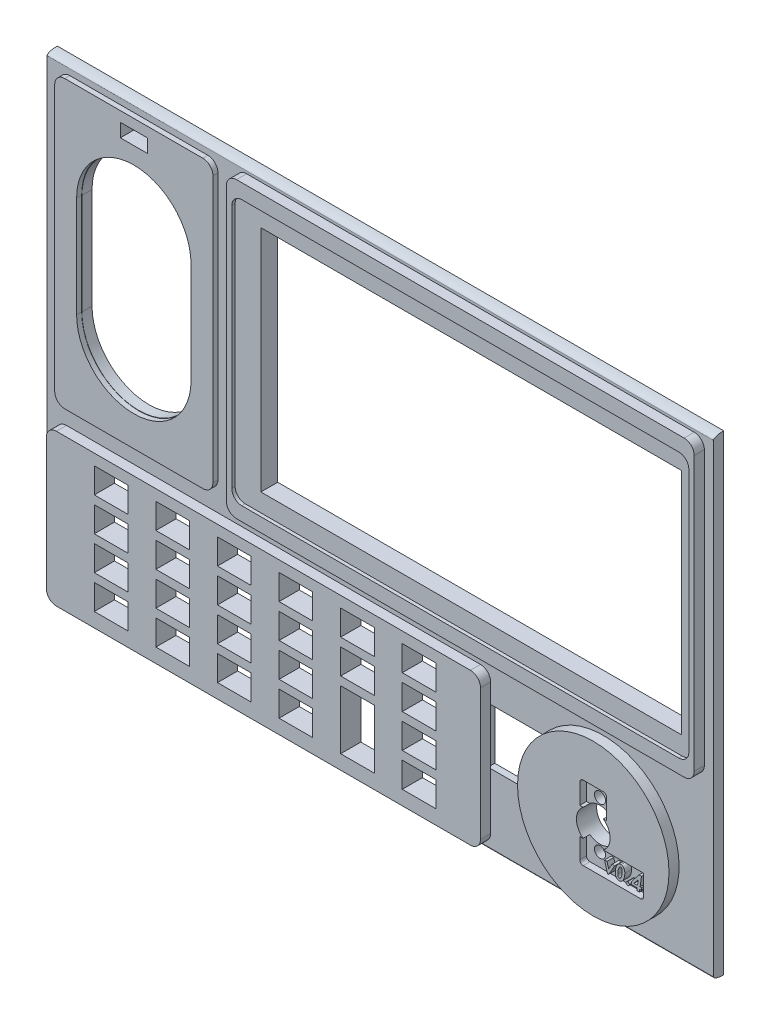
SolidWorks part; units mm, degrees
ref_plane "Front Plane" through (0, 0, 0) normal (0, 0, 1) x (1, 0, 0)
ref_plane "Top Plane" through (0, 0, 0) normal (0, 1, 0) x (1, 0, 0)
ref_plane "Right Plane" through (0, 0, 0) normal (1, 0, 0) x (0, 0, -1)
sketch "Sketch1" plane through (0, 0, 0) normal (0, 0, 1) x (1, 0, 0)
  line L1 (99, -70) -> (-99, -70)
  line L2 (99, -70) -> (99, 70)
  line L3 (99, 70) -> (-99, 70)
  line L4 (-99, -70) -> (-99, 70)
  line L5 (99, -70) -> (-99, 70) construction
  line L6 (99, 70) -> (-99, -70) construction
  point P0 (0, 0)
  dimension "D1" = 198
  dimension "D2" = 140
extrude "main_body" add sketch "Sketch1" along normal blind 3
fillet "long_corners" radius 3 2 edges at (0, 70, 3) (0, -70, 3) second distance 1 first distance on face at (0, 70, 1.5) first distance on face at (0, -70, 1.5)
sketch "Sketch2" plane through (0, 0, 3) normal (0, 0, 1) x (1, 0, 0)
  line L0 (-99, 24.75) -> (99, 24.75) construction
  line L1 (-99, 69) -> (-99, -69) construction
  line L2 (99, -69) -> (99, 69) construction
  line L3 (99, 69) -> (-99, 69) construction
  line L4 (-48.25, -17.75) -> (-95.25, -17.75)
  line L5 (-48.25, -17.75) -> (-48.25, 67.25)
  line L6 (-48.25, 67.25) -> (-95.25, 67.25)
  line L7 (-95.25, -17.75) -> (-95.25, 67.25)
  line L8 (-48.25, -17.75) -> (-95.25, 67.25) construction
  line L9 (-48.25, 67.25) -> (-95.25, -17.75) construction
  point P6 (-71.75, 24.75)
  dimension "D1" = 85
  dimension "D2" = 47
  dimension "D3" = 27.25
  dimension "D4" = 44.25
extrude "speaker" add sketch "Sketch2" along normal blind 1.5
fillet "speaker_corners" radius 3 4 edges at (-95.25, 67.25, 3.75) (-95.25, -17.75, 3.75) (-48.25, -17.75, 3.75) (-48.25, 67.25, 3.75)
sketch "Sketch19" plane through (0, 0, 4.5) normal (0, 0, 1) x (1, 0, 0)
  line L0 (-71.75, 67.25) -> (-71.75, -17.75) construction
  line L1 (-51.25, 67.25) -> (-92.25, 67.25) construction
  line L2 (-92.25, -17.75) -> (-51.25, -17.75) construction
  line L3 (-71.75, 8.25) -> (-71.75, 38.25) construction
  line L4 (-95.25, 64.25) -> (-95.25, -14.75) construction
  line L5 (-95.25, 24.75) -> (-48.25, 24.75) construction
  line L6 (-48.25, -14.75) -> (-48.25, 64.25) construction
  line L7 (-88.75, 8.25) -> (-88.75, 38.25)
  line L8 (-54.75, 8.25) -> (-54.75, 38.25)
  arc A0 (-88.75, 8.25) -> (-54.75, 8.25) centre (-71.75, 8.25) ccw
  arc A1 (-54.75, 38.25) -> (-88.75, 38.25) centre (-71.75, 38.25) ccw
  point P14 (-71.75, 23.25)
  point P19 (-71.75, -8.75)
  point P20 (-71.75, 55.25)
  dimension "D2" = 64
  dimension "D1" = 34
  dimension "D3" = 12
extrude "speaker_cut" cut sketch "Sketch19" against normal through all
sketch "Sketch21" plane through (0, 0, 0) normal (0, 0, -1) x (-1, 0, 0)
  line L0 (71.75, -8.75) -> (71.75, 55.25) construction
  line L2 (54.75, 8.25) -> (54.75, 38.25) construction
  line L3 (54.75, 23.25) -> (88.75, 23.25) construction
  line L4 (88.75, 38.25) -> (88.75, 8.25) construction
  line L5 (50.25, 59.25) -> (93.25, 59.25)
  line L6 (50.25, 59.25) -> (50.25, -12.75)
  line L7 (50.25, -12.75) -> (93.25, -12.75)
  line L8 (93.25, 59.25) -> (93.25, -12.75)
  line L9 (50.25, 59.25) -> (93.25, -12.75) construction
  line L10 (50.25, -12.75) -> (93.25, 59.25) construction
  arc A0 (54.75, 8.25) -> (88.75, 8.25) centre (71.75, 8.25) ccw construction
  arc A1 (88.75, 38.25) -> (54.75, 38.25) centre (71.75, 38.25) ccw construction
  point P14 (71.75, 23.25)
  dimension "D1" = 43
  dimension "D2" = 72
extrude "speaker_slot" cut sketch "Sketch21" against normal blind 3
sketch "Sketch36" plane through (0, 0, 3) normal (0, 0, -1) x (-1, 0, 0)
  line L0 (50.25, 23.25) -> (93.25, 23.25) construction
  line L1 (50.25, 59.25) -> (50.25, -12.75) construction
  line L2 (71.75, 8.2639) -> (71.75, 38.2361) construction
  line L3 (71.75, 8.2639) -> (71.75, 38.2361) construction
  line L4 (93.25, -12.75) -> (93.25, 59.25) construction
  line L5 (50.25, 59.25) -> (50.25, -12.75) construction
  line L6 (54.8316, 8.2639) -> (54.8316, 38.2361)
  line L9 (88.6684, 8.2639) -> (88.6684, 38.2361)
  line L10 (54.25, 8.2639) -> (54.25, 38.2361)
  line L11 (89.25, 8.2639) -> (89.25, 38.2361)
  line L12 (93.25, 59.25) -> (50.25, 59.25) construction
  line L13 (71.75, 59.25) -> (71.75, -12.75) construction
  line L14 (50.25, -12.75) -> (93.25, -12.75) construction
  line L23 (50.25, 57.25) -> (93.25, 57.25)
  line L25 (50.25, 57.25) -> (50.25, 56.75)
  line L26 (93.25, -0.25) -> (87.75, -0.25)
  line L27 (50.25, 56.75) -> (93.25, 56.75)
  line L28 (93.25, 57.25) -> (93.25, 56.75)
  line L37 (93.25, -12.75) -> (93.25, 59.25) construction
  line L38 (93.25, -0.25) -> (93.25, 0.25)
  line L39 (93.25, 0.25) -> (87.75, 0.25)
  line L48 (93.25, -10.75) -> (50.25, -10.75)
  line L49 (93.25, -10.75) -> (93.25, -10.25)
  line L50 (93.25, -10.25) -> (50.25, -10.25)
  line L51 (50.25, -10.75) -> (50.25, -10.25)
  line L52 (93.25, 46.75) -> (87.75, 46.75)
  line L53 (93.25, 46.75) -> (93.25, 46.25)
  line L54 (93.25, 46.25) -> (87.75, 46.25)
  line L55 (87.75, 46.75) -> (87.75, 46.25)
  line L56 (93.25, 35.25) -> (89.75, 35.25)
  line L57 (93.25, 35.25) -> (93.25, 34.75)
  line L58 (93.25, 34.75) -> (89.75, 34.75)
  line L59 (89.75, 35.25) -> (89.75, 34.75)
  line L60 (93.25, 23.25) -> (89.75, 23.25)
  line L61 (93.25, 23.25) -> (93.25, 23.75)
  line L62 (93.25, 23.75) -> (89.75, 23.75)
  line L63 (89.75, 23.25) -> (89.75, 23.75)
  line L64 (93.25, 10.75) -> (89.75, 10.75)
  line L65 (93.25, 10.75) -> (93.25, 11.25)
  line L66 (93.25, 11.25) -> (89.75, 11.25)
  line L67 (89.75, 10.75) -> (89.75, 11.25)
  line L68 (87.75, -0.25) -> (87.75, 0.25)
  line L69 (93.25, -5.25) -> (83.25, -5.25)
  line L70 (93.25, -5.25) -> (93.25, -5.75)
  line L71 (93.25, -5.75) -> (83.25, -5.75)
  line L72 (83.25, -5.25) -> (83.25, -5.75)
  line L73 (93.25, 52.25) -> (83.25, 52.25)
  line L74 (93.25, 52.25) -> (93.25, 51.75)
  line L75 (93.25, 51.75) -> (83.25, 51.75)
  line L76 (83.25, 52.25) -> (83.25, 51.75)
  line L77 (50.25, 52.25) -> (60.25, 52.25)
  line L78 (50.25, 52.25) -> (50.25, 51.75)
  line L79 (50.25, 51.75) -> (60.25, 51.75)
  line L80 (60.25, 52.25) -> (60.25, 51.75)
  line L81 (50.25, 46.75) -> (55.75, 46.75)
  line L82 (50.25, 46.75) -> (50.25, 46.25)
  line L83 (50.25, 46.25) -> (55.75, 46.25)
  line L84 (55.75, 46.75) -> (55.75, 46.25)
  line L85 (50.25, 35.25) -> (53.75, 35.25)
  line L86 (50.25, 35.25) -> (50.25, 34.75)
  line L87 (50.25, 34.75) -> (53.75, 34.75)
  line L88 (53.75, 35.25) -> (53.75, 34.75)
  line L89 (50.25, 23.25) -> (53.75, 23.25)
  line L90 (50.25, 23.25) -> (50.25, 23.75)
  line L91 (50.25, 23.75) -> (53.75, 23.75)
  line L92 (53.75, 23.25) -> (53.75, 23.75)
  line L93 (50.25, 10.25) -> (53.75, 10.25)
  line L94 (50.25, 10.25) -> (50.25, 10.75)
  line L95 (50.25, 10.75) -> (53.75, 10.75)
  line L96 (53.75, 10.25) -> (53.75, 10.75)
  line L97 (50.25, -0.25) -> (55.75, -0.25)
  line L98 (50.25, -0.25) -> (50.25, 0.25)
  line L99 (50.25, 0.25) -> (55.75, 0.25)
  line L100 (55.75, -0.25) -> (55.75, 0.25)
  line L101 (50.25, -5.25) -> (60.25, -5.25)
  line L102 (50.25, -5.25) -> (50.25, -5.75)
  line L103 (50.25, -5.75) -> (60.25, -5.75)
  line L104 (60.25, -5.25) -> (60.25, -5.75)
  arc A0 (54.25, 8.2639) -> (89.25, 8.2639) centre (71.75, 8.2639) ccw
  arc A1 (89.25, 38.2361) -> (54.25, 38.2361) centre (71.75, 38.2361) ccw
  arc A4 (54.8316, 8.2639) -> (88.6684, 8.2639) centre (71.75, 8.2639) ccw
  arc A5 (88.6684, 38.2361) -> (54.8316, 38.2361) centre (71.75, 38.2361) ccw
  point P6 (71.75, 23.25)
  point P22 (71.75, 23.25)
  point P31 (89.25, 23.25)
  point P32 (71.75, 55.1546)
  point P33 (71.75, -8.6546)
  point P95 (52, 35.25)
  point P96 (55.25, 51.75)
  point P97 (91.5, 10.75)
  dimension "D48" = 0.5816
  dimension "D1" = 33.8368
  dimension "D2" = 35
  dimension "D3" = 63.8091
  dimension "D4" = 0.5
  dimension "D5" = 0.5
  dimension "D6" = 0.5
  dimension "D7" = 0.5
  dimension "D8" = 0.5
  dimension "D9" = 11
  dimension "D10" = 11
  dimension "D11" = 5
  dimension "D12" = 4.5
  dimension "D13" = 10
  dimension "D14" = 5.5
  dimension "D15" = 3.5
  dimension "D16" = 3.5
  dimension "D17" = 0.5
  dimension "D18" = 0.5
  dimension "D19" = 0.5
  dimension "D20" = 0.5
  dimension "D21" = 11
  dimension "D22" = 11
  dimension "D23" = 5
  dimension "D24" = 10
  dimension "D25" = 5.5
  dimension "D26" = 3.5
  dimension "D27" = 3.5
  dimension "D28" = 0.5
  dimension "D29" = 0.5
  dimension "D30" = 0.5
  dimension "D31" = 0.5
  dimension "D32" = 0.5
  dimension "D33" = 0.5
  dimension "D34" = 0.5
  dimension "D35" = 12
  dimension "D36" = 10.5
  dimension "D37" = 5.5
  dimension "D38" = 5
  dimension "D39" = 4.5
  dimension "D40" = 3.5
  dimension "D41" = 10
  dimension "D42" = 4.5
  dimension "D43" = 5
  dimension "D44" = 10
  dimension "D45" = 3.5
  dimension "D46" = 5.5
  dimension "D47" = 10
extrude "speaker_print_support" add sketch "Sketch36" along normal blind 3
sketch "Sketch3" plane through (0, 0, 3) normal (0, 0, 1) x (1, 0, 0)
  line L0 (-99, 24.625) -> (99, 24.625) construction
  line L1 (-99, 69) -> (-99, -69) construction
  line L2 (99, -69) -> (99, 69) construction
  line L4 (-48.25, -14.75) -> (-48.25, 64.25) construction
  line L5 (96.25, -19) -> (-42.75, -19)
  line L6 (96.25, -19) -> (96.25, 68.25)
  line L7 (96.25, 68.25) -> (-42.75, 68.25)
  line L8 (-42.75, -19) -> (-42.75, 68.25)
  line L9 (96.25, -19) -> (-42.75, 68.25) construction
  line L10 (96.25, 68.25) -> (-42.75, -19) construction
  line L11 (99, 70) -> (-99, 70) construction
  point P8 (26.75, 24.625)
  dimension "D1" = 1.75
  dimension "D2" = 87.25
  dimension "D3" = 139
  dimension "D4" = 2.75
  dimension "D5" = 5.5
extrude "lcd" add sketch "Sketch3" along normal blind 3
fillet "lcd_corners" radius 3 4 edges at (96.25, -19, 4.5) (-42.75, -19, 4.5) (96.25, 68.25, 4.5) (-42.75, 68.25, 4.5)
sketch "Sketch9" plane through (0, 0, 6) normal (0, 0, 1) x (1, 0, 0)
  line L0 (-42.75, 24.5) -> (96.25, 24.5) construction
  line L1 (-42.75, 65.25) -> (-42.75, -16) construction
  line L2 (96.25, -16) -> (96.25, 65.25) construction
  line L3 (-39.75, -19) -> (93.25, -19) construction
  line L4 (94.65, -14.875) -> (-41.15, -14.875)
  line L5 (94.65, -14.875) -> (94.65, 63.875)
  line L6 (94.65, 63.875) -> (-41.15, 63.875)
  line L7 (-41.15, -14.875) -> (-41.15, 63.875)
  line L8 (94.65, -14.875) -> (-41.15, 63.875) construction
  line L9 (94.65, 63.875) -> (-41.15, -14.875) construction
  line L10 (93.25, 68.25) -> (-39.75, 68.25) construction
  line L11 (96.25, -16) -> (96.25, 65.25) construction
  point P6 (26.75, 24.5)
  dimension "D1" = 135.8
  dimension "D2" = 78.75
  dimension "D3" = 1.6
  dimension "D4" = 4.125
  dimension "D5" = 4.375
  dimension "D6" = 1.6
extrude "lcd_front" cut sketch "Sketch9" against normal blind 1
fillet "lcd_front_corners" radius 3 4 edges at (94.65, -14.875, 5.5) (94.65, 63.875, 5.5) (-41.15, 63.875, 5.5) (-41.15, -14.875, 5.5)
sketch "Sketch10" plane through (0, 0, 0) normal (0, 0, -1) x (-1, 0, 0)
  line L0 (-94.65, -11.875) -> (-94.65, 60.875) construction
  line L1 (-91.65, 63.875) -> (38.15, 63.875) construction
  line L2 (41.15, 63.875) -> (41.15, -14.875) construction
  line L3 (-94.65, 63.875) -> (41.15, 63.875) construction
  line L4 (33.5, -9.5) -> (-91.5, -9.5)
  line L5 (33.5, -9.5) -> (33.5, 58.5)
  line L6 (33.5, 58.5) -> (-91.5, 58.5)
  line L7 (-91.5, -9.5) -> (-91.5, 58.5)
  line L8 (-91.5, -9.5) -> (33.5, 58.5) construction
  line L9 (-91.5, 58.5) -> (33.5, -9.5) construction
  line L10 (-99, -70) -> (-99, 70) construction
  line L11 (-99, 70) -> (99, 70) construction
  line L13 (38.15, -14.875) -> (-91.65, -14.875) construction
  dimension "D1" = 125
  dimension "D2" = 68
  dimension "D3" = 7.5
  dimension "D4" = 7.65
  dimension "D5" = 11.5
  dimension "D6" = 5.375
  dimension "D7" = 3.15
  dimension "D8" = 5.375
  dimension "D9" = 5.375
extrude "lcd_back" cut sketch "Sketch10" against normal through all
sketch "Sketch4" plane through (0, 0, 3) normal (0, 0, 1) x (1, 0, 0)
  line L0 (-99, -45.75) -> (99, -45.75) construction
  line L1 (-99, 69) -> (-99, -69) construction
  line L2 (99, -69) -> (99, 69) construction
  line L4 (-92.25, -17.75) -> (-51.25, -17.75) construction
  line L5 (32.75, -68.25) -> (-96.25, -68.25)
  line L6 (32.75, -68.25) -> (32.75, -23.25)
  line L7 (32.75, -23.25) -> (-96.25, -23.25)
  line L8 (-96.25, -68.25) -> (-96.25, -23.25)
  line L9 (32.75, -68.25) -> (-96.25, -23.25) construction
  line L10 (32.75, -23.25) -> (-96.25, -68.25) construction
  line L11 (-99, -70) -> (99, -70) construction
  point P8 (-31.75, -45.75)
  dimension "D1" = 1.75
  dimension "D2" = 129
  dimension "D3" = 45
  dimension "D4" = 2.75
  dimension "D5" = 5.5
extrude "keypad" add sketch "Sketch4" along normal blind 3
fillet "keypad_corners" radius 3 4 edges at (-96.25, -68.25, 4.5) (32.75, -68.25, 4.5) (32.75, -23.25, 4.5) (-96.25, -23.25, 4.5)
sketch "Sketch25" plane through (0, 0, 6) normal (0, 0, 1) x (1, 0, 0)
  line L0 (-96.25, -30.25) -> (32.75, -30.25) construction
  line L1 (29.75, -23.25) -> (-93.25, -23.25) construction
  line L2 (-93.25, -68.25) -> (29.75, -68.25) construction
  line L3 (-77, -23.25) -> (-77, -68.25) construction
  line L5 (-35.4, -64) -> (32.75, -64) construction
  line L6 (-96.25, -26.25) -> (-96.25, -65.25) construction
  line L11 (32.75, -65.25) -> (32.75, -26.25) construction
  line L12 (-58.7, -23.25) -> (-58.7, -68.25) construction
  line L13 (-96.25, -40.25) -> (32.75, -40.25) construction
  line L14 (29.75, -23.25) -> (-93.25, -23.25) construction
  line L15 (-40.4, -23.25) -> (-40.4, -68.25) construction
  line L16 (-93.25, -68.25) -> (29.75, -68.25) construction
  line L17 (-72, -34) -> (-82, -34)
  line L18 (-22.1, -23.25) -> (-22.1, -68.25) construction
  line L19 (-96.25, -50.25) -> (32.75, -50.25) construction
  line L20 (-3.8, -23.25) -> (-3.8, -68.25) construction
  line L21 (-72, -34) -> (-72, -26.5)
  line L22 (14.5, -23.25) -> (14.5, -68.25) construction
  line L23 (-96.25, -26.25) -> (-96.25, -65.25) construction
  line L24 (-96.25, -60.25) -> (32.75, -60.25) construction
  line L25 (-72, -26.5) -> (-82, -26.5)
  line L26 (-82, -34) -> (-82, -26.5)
  line L27 (-72, -34) -> (-82, -26.5) construction
  line L28 (-72, -26.5) -> (-82, -34) construction
  line L29 (-72, -44) -> (-82, -44)
  line L30 (-72, -44) -> (-72, -36.5)
  line L31 (-72, -36.5) -> (-82, -36.5)
  line L32 (-82, -44) -> (-82, -36.5)
  line L33 (-72, -44) -> (-82, -36.5) construction
  line L34 (-72, -36.5) -> (-82, -44) construction
  line L35 (-72, -54) -> (-82, -54)
  line L36 (-72, -54) -> (-72, -46.5)
  line L37 (-72, -46.5) -> (-82, -46.5)
  line L38 (-82, -54) -> (-82, -46.5)
  line L39 (-72, -54) -> (-82, -46.5) construction
  line L40 (-72, -46.5) -> (-82, -54) construction
  line L41 (-72, -64) -> (-82, -64)
  line L42 (-72, -64) -> (-72, -56.5)
  line L43 (-72, -56.5) -> (-82, -56.5)
  line L44 (-82, -64) -> (-82, -56.5)
  line L45 (-72, -64) -> (-82, -56.5) construction
  line L46 (-72, -56.5) -> (-82, -64) construction
  line L47 (-53.7, -34) -> (-63.7, -34)
  line L48 (-53.7, -34) -> (-53.7, -26.5)
  line L49 (-53.7, -26.5) -> (-63.7, -26.5)
  line L50 (-63.7, -34) -> (-63.7, -26.5)
  line L51 (-53.7, -34) -> (-63.7, -26.5) construction
  line L52 (-53.7, -26.5) -> (-63.7, -34) construction
  line L53 (-53.7, -44) -> (-63.7, -44)
  line L54 (-53.7, -44) -> (-53.7, -36.5)
  line L55 (-53.7, -36.5) -> (-63.7, -36.5)
  line L56 (-63.7, -44) -> (-63.7, -36.5)
  line L57 (-53.7, -44) -> (-63.7, -36.5) construction
  line L58 (-53.7, -36.5) -> (-63.7, -44) construction
  line L59 (-53.7, -54) -> (-63.7, -54)
  line L60 (-53.7, -54) -> (-53.7, -46.5)
  line L61 (-53.7, -46.5) -> (-63.7, -46.5)
  line L62 (-63.7, -54) -> (-63.7, -46.5)
  line L63 (-53.7, -54) -> (-63.7, -46.5) construction
  line L64 (-53.7, -46.5) -> (-63.7, -54) construction
  line L65 (-53.7, -64) -> (-63.7, -64)
  line L66 (-53.7, -64) -> (-53.7, -56.5)
  line L67 (-53.7, -56.5) -> (-63.7, -56.5)
  line L68 (-63.7, -64) -> (-63.7, -56.5)
  line L69 (-53.7, -64) -> (-63.7, -56.5) construction
  line L70 (-53.7, -56.5) -> (-63.7, -64) construction
  line L71 (-35.4, -34) -> (-45.4, -34)
  line L72 (-35.4, -34) -> (-35.4, -26.5)
  line L73 (-35.4, -26.5) -> (-45.4, -26.5)
  line L74 (-45.4, -34) -> (-45.4, -26.5)
  line L75 (-35.4, -34) -> (-45.4, -26.5) construction
  line L76 (-35.4, -26.5) -> (-45.4, -34) construction
  line L77 (-35.4, -44) -> (-45.4, -44)
  line L78 (-35.4, -44) -> (-35.4, -36.5)
  line L79 (-35.4, -36.5) -> (-45.4, -36.5)
  line L80 (-45.4, -44) -> (-45.4, -36.5)
  line L81 (-35.4, -44) -> (-45.4, -36.5) construction
  line L82 (-35.4, -36.5) -> (-45.4, -44) construction
  line L83 (-35.4, -54) -> (-45.4, -54)
  line L84 (-35.4, -54) -> (-35.4, -46.5)
  line L85 (-35.4, -46.5) -> (-45.4, -46.5)
  line L86 (-45.4, -54) -> (-45.4, -46.5)
  line L87 (-35.4, -54) -> (-45.4, -46.5) construction
  line L88 (-35.4, -46.5) -> (-45.4, -54) construction
  line L89 (-35.4, -64) -> (-45.4, -64)
  line L90 (-35.4, -64) -> (-35.4, -56.5)
  line L91 (-35.4, -56.5) -> (-45.4, -56.5)
  line L92 (-45.4, -64) -> (-45.4, -56.5)
  line L93 (-35.4, -64) -> (-45.4, -56.5) construction
  line L94 (-35.4, -56.5) -> (-45.4, -64) construction
  line L95 (-17.1, -34) -> (-27.1, -34)
  line L96 (-17.1, -34) -> (-17.1, -26.5)
  line L97 (-17.1, -26.5) -> (-27.1, -26.5)
  line L98 (-27.1, -34) -> (-27.1, -26.5)
  line L99 (-17.1, -34) -> (-27.1, -26.5) construction
  line L100 (-17.1, -26.5) -> (-27.1, -34) construction
  line L101 (-17.1, -44) -> (-27.1, -44)
  line L102 (-17.1, -44) -> (-17.1, -36.5)
  line L103 (-17.1, -36.5) -> (-27.1, -36.5)
  line L104 (-27.1, -44) -> (-27.1, -36.5)
  line L105 (-17.1, -44) -> (-27.1, -36.5) construction
  line L106 (-17.1, -36.5) -> (-27.1, -44) construction
  line L111 (-17.1, -54) -> (-27.1, -54)
  line L112 (-17.1, -54) -> (-17.1, -46.5)
  line L113 (-17.1, -46.5) -> (-27.1, -46.5)
  line L114 (-27.1, -54) -> (-27.1, -46.5)
  line L115 (-17.1, -54) -> (-27.1, -46.5) construction
  line L116 (-17.1, -46.5) -> (-27.1, -54) construction
  line L117 (-17.1, -64) -> (-27.1, -64)
  line L118 (-17.1, -64) -> (-17.1, -56.5)
  line L119 (-17.1, -56.5) -> (-27.1, -56.5)
  line L120 (-27.1, -64) -> (-27.1, -56.5)
  line L121 (-17.1, -64) -> (-27.1, -56.5) construction
  line L122 (-17.1, -56.5) -> (-27.1, -64) construction
  line L127 (1.2, -34) -> (-8.8, -34)
  line L128 (1.2, -34) -> (1.2, -26.5)
  line L129 (1.2, -26.5) -> (-8.8, -26.5)
  line L130 (-8.8, -34) -> (-8.8, -26.5)
  line L131 (1.2, -34) -> (-8.8, -26.5) construction
  line L132 (1.2, -26.5) -> (-8.8, -34) construction
  line L133 (19.5, -34) -> (9.5, -34)
  line L134 (19.5, -34) -> (19.5, -26.5)
  line L135 (19.5, -26.5) -> (9.5, -26.5)
  line L136 (9.5, -34) -> (9.5, -26.5)
  line L137 (19.5, -34) -> (9.5, -26.5) construction
  line L138 (19.5, -26.5) -> (9.5, -34) construction
  line L139 (1.2, -44) -> (-8.8, -44)
  line L140 (1.2, -44) -> (1.2, -36.5)
  line L141 (1.2, -36.5) -> (-8.8, -36.5)
  line L142 (-8.8, -44) -> (-8.8, -36.5)
  line L143 (1.2, -44) -> (-8.8, -36.5) construction
  line L144 (1.2, -36.5) -> (-8.8, -44) construction
  line L145 (19.5, -44) -> (9.5, -44)
  line L146 (19.5, -44) -> (19.5, -36.5)
  line L147 (19.5, -36.5) -> (9.5, -36.5)
  line L148 (9.5, -44) -> (9.5, -36.5)
  line L149 (19.5, -44) -> (9.5, -36.5) construction
  line L150 (19.5, -36.5) -> (9.5, -44) construction
  line L151 (19.5, -54) -> (9.5, -54)
  line L152 (19.5, -54) -> (19.5, -46.5)
  line L153 (19.5, -46.5) -> (9.5, -46.5)
  line L154 (9.5, -54) -> (9.5, -46.5)
  line L155 (19.5, -54) -> (9.5, -46.5) construction
  line L156 (19.5, -46.5) -> (9.5, -54) construction
  line L157 (19.5, -64) -> (9.5, -64)
  line L158 (19.5, -64) -> (19.5, -56.5)
  line L159 (19.5, -56.5) -> (9.5, -56.5)
  line L160 (9.5, -64) -> (9.5, -56.5)
  line L161 (19.5, -64) -> (9.5, -56.5) construction
  line L162 (19.5, -56.5) -> (9.5, -64) construction
  line L163 (1.2, -64) -> (-8.8, -64)
  line L164 (1.2, -64) -> (1.2, -46.5)
  line L165 (1.2, -46.5) -> (-8.8, -46.5)
  line L166 (-8.8, -64) -> (-8.8, -46.5)
  line L167 (1.2, -64) -> (-8.8, -46.5) construction
  line L168 (1.2, -46.5) -> (-8.8, -64) construction
  point P34 (-77, -30.25)
  point P39 (-77, -40.25)
  point P44 (-77, -50.25)
  point P49 (-77, -60.25)
  point P54 (-58.7, -30.25)
  point P59 (-58.7, -40.25)
  point P64 (-58.7, -50.25)
  point P69 (-58.7, -60.25)
  point P74 (-40.4, -30.25)
  point P79 (-40.4, -40.25)
  point P84 (-40.4, -50.25)
  point P89 (-40.4, -60.25)
  point P94 (-22.1, -30.25)
  point P99 (-22.1, -40.25)
  point P104 (-22.1, -50.25)
  point P109 (-22.1, -60.25)
  point P114 (-3.8, -30.25)
  point P119 (14.5, -30.25)
  point P124 (-3.8, -40.25)
  point P129 (14.5, -40.25)
  point P134 (14.5, -50.25)
  point P139 (14.5, -60.25)
  point P144 (-3.8, -55.25)
  dimension "D1" = 18.25
  dimension "D2" = 18.3
  dimension "D3" = 18.3
  dimension "D4" = 18.3
  dimension "D5" = 18.3
  dimension "D6" = 18.3
  dimension "D7" = 19.25
  dimension "D8" = 7
  dimension "D9" = 10
  dimension "D10" = 10
  dimension "D11" = 10
  dimension "D12" = 8
  dimension "D13" = 10
  dimension "D14" = 10
  dimension "D15" = 10
  dimension "D16" = 10
  dimension "D17" = 10
  dimension "D18" = 10
  dimension "D19" = 10
  dimension "D20" = 10
  dimension "D21" = 10
  dimension "D22" = 10
  dimension "D23" = 10
  dimension "D24" = 10
  dimension "D25" = 10
  dimension "D26" = 10
  dimension "D27" = 10
  dimension "D28" = 10
  dimension "D29" = 10
  dimension "D30" = 10
  dimension "D31" = 10
  dimension "D32" = 10
  dimension "D33" = 10
  dimension "D34" = 10
  dimension "D35" = 10
  dimension "D36" = 7.5
  dimension "D37" = 7.5
  dimension "D38" = 7.5
  dimension "D39" = 7.5
  dimension "D40" = 7.5
  dimension "D41" = 7.5
  dimension "D42" = 17.5
  dimension "D43" = 7.5
  dimension "D44" = 7.5
  dimension "D45" = 7.5
  dimension "D46" = 7.5
  dimension "D47" = 7.5
  dimension "D48" = 7.5
  dimension "D49" = 7.5
  dimension "D50" = 7.5
  dimension "D51" = 7.5
  dimension "D52" = 7.5
  dimension "D53" = 7.5
  dimension "D54" = 7.5
  dimension "D55" = 7.5
  dimension "D56" = 7.5
  dimension "D57" = 7.5
  dimension "D58" = 7.5
  dimension "D59" = 5
extrude "keypad_cuts_0.8" cut sketch "Sketch25" against normal through all
sketch "Sketch40" plane through (0, 0, 6) normal (0, 0, 1) x (1, 0, 0)
  line L0 (16.75, -23.25) -> (16.75, -68.25) construction
  line L1 (-8.25, -23.25) -> (-8.25, -68.25) construction
  line L2 (-67.25, -23.25) -> (-67.25, -68.25) construction
  line L3 (-96.25, -45.75) -> (32.75, -45.75) construction
  line L4 (-83.25, -23.25) -> (-83.25, -68.25) construction
  line L5 (29.75, -23.25) -> (-93.25, -23.25) construction
  line L6 (-93.25, -68.25) -> (29.75, -68.25) construction
  line L11 (-77.25, -49.75) -> (-89.25, -49.75)
  line L12 (-77.25, -49.75) -> (-77.25, -41.75)
  line L13 (-93.25, -68.25) -> (29.75, -68.25) construction
  line L14 (-77.25, -41.75) -> (-89.25, -41.75)
  line L15 (-89.25, -49.75) -> (-89.25, -41.75)
  line L16 (-35.25, -68.25) -> (-35.25, -23.25) construction
  line L18 (29.75, -23.25) -> (-93.25, -23.25) construction
  line L19 (-77.25, -49.75) -> (-89.25, -41.75) construction
  line L20 (-51.25, -68.25) -> (-51.25, -23.25) construction
  line L22 (-77.25, -41.75) -> (-89.25, -49.75) construction
  line L23 (-61.25, -49.75) -> (-73.25, -49.75)
  line L24 (-61.25, -49.75) -> (-61.25, -41.75)
  line L25 (-61.25, -41.75) -> (-73.25, -41.75)
  line L26 (-73.25, -49.75) -> (-73.25, -41.75)
  line L27 (-61.25, -49.75) -> (-73.25, -41.75) construction
  line L28 (-61.25, -41.75) -> (-73.25, -49.75) construction
  line L29 (-45.25, -49.75) -> (-57.25, -49.75)
  line L30 (-45.25, -49.75) -> (-45.25, -41.75)
  line L31 (-45.25, -41.75) -> (-57.25, -41.75)
  line L32 (-57.25, -49.75) -> (-57.25, -41.75)
  line L33 (-45.25, -49.75) -> (-57.25, -41.75) construction
  line L34 (-45.25, -41.75) -> (-57.25, -49.75) construction
  line L35 (-29.25, -49.75) -> (-41.25, -49.75)
  line L36 (-29.25, -49.75) -> (-29.25, -41.75)
  line L37 (-29.25, -41.75) -> (-41.25, -41.75)
  line L38 (-41.25, -49.75) -> (-41.25, -41.75)
  line L39 (-29.25, -49.75) -> (-41.25, -41.75) construction
  line L40 (-29.25, -41.75) -> (-41.25, -49.75) construction
  line L45 (-2.25, -41.75) -> (-14.25, -41.75)
  line L46 (-2.25, -41.75) -> (-2.25, -33.75)
  line L51 (-2.25, -33.75) -> (-14.25, -33.75)
  line L52 (-14.25, -41.75) -> (-14.25, -33.75)
  line L53 (22.75, -35.75) -> (10.75, -35.75)
  line L54 (22.75, -35.75) -> (22.75, -27.75)
  line L55 (22.75, -27.75) -> (10.75, -27.75)
  line L56 (10.75, -35.75) -> (10.75, -27.75)
  line L57 (22.75, -35.75) -> (10.75, -27.75) construction
  line L58 (22.75, -27.75) -> (10.75, -35.75) construction
  line L59 (22.75, -63.75) -> (10.75, -63.75)
  line L60 (22.75, -63.75) -> (22.75, -55.75)
  line L61 (22.75, -55.75) -> (10.75, -55.75)
  line L62 (10.75, -63.75) -> (10.75, -55.75)
  line L63 (22.75, -63.75) -> (10.75, -55.75) construction
  line L64 (22.75, -55.75) -> (10.75, -63.75) construction
  line L69 (32.75, -65.25) -> (32.75, -26.25) construction
  line L70 (-2.25, -57.25) -> (-14.25, -57.25)
  line L75 (-2.25, -57.25) -> (-2.25, -49.25)
  line L76 (-2.25, -49.25) -> (-14.25, -49.25)
  line L77 (-2.25, -41.75) -> (-14.25, -33.75) construction
  line L78 (-2.25, -33.75) -> (-14.25, -41.75) construction
  line L85 (-14.25, -57.25) -> (-14.25, -49.25)
  line L86 (-2.25, -57.25) -> (-14.25, -49.25) construction
  line L87 (-2.25, -49.25) -> (-14.25, -57.25) construction
  line L88 (-96.25, -26.25) -> (-96.25, -65.25) construction
  line L89 (32.75, -65.25) -> (32.75, -26.25) construction
  line L93 (32.75, -59.75) -> (-96.25, -59.75) construction
  line L94 (-96.25, -31.75) -> (32.75, -31.75) construction
  line L95 (32.75, -31.75) -> (32.75, -37.75) construction
  line L96 (32.75, -37.75) -> (-96.25, -37.75) construction
  line L99 (-96.25, -26.25) -> (-96.25, -65.25) construction
  line L100 (-96.25, -53.75) -> (32.75, -53.75) construction
  point P18 (-83.25, -45.75)
  point P25 (-67.25, -45.75)
  point P30 (-51.25, -45.75)
  point P35 (-35.25, -45.75)
  point P40 (-8.25, -37.75)
  point P45 (-8.25, -53.25)
  point P50 (16.75, -31.75)
  point P55 (16.75, -59.75)
  dimension "D1" = 8
  dimension "D2" = 8
  dimension "D3" = 8
  dimension "D4" = 8
  dimension "D5" = 8
  dimension "D6" = 12
  dimension "D7" = 8
  dimension "D8" = 8
  dimension "D9" = 12
  dimension "D10" = 12
  dimension "D11" = 12
  dimension "D12" = 12
  dimension "D13" = 12
  dimension "D14" = 12
  dimension "D15" = 8
  dimension "D16" = 12
  dimension "D17" = 8
  dimension "D18" = 8
  dimension "D19" = 27
  dimension "D20" = 14
  dimension "D21" = 16
  dimension "D22" = 16
  dimension "D23" = 16
  dimension "D24" = 25
  dimension "D25" = 14
extrude "keypad_cuts_0.7" [suppressed] cut sketch "Sketch40" against normal through all
sketch "Sketch41" [suppressed] plane through (0, 0, 0) normal (0, 0, -1) x (-1, 0, 0)
  line L0 (-22.75, -27.75) -> (-10.75, -35.75) construction
  line L1 (-22.75, -55.75) -> (-10.75, -63.75) construction
  line L2 (8.25, -33.75) -> (8.25, -57.25) construction
  line L3 (-10.75, -63.75) -> (-22.75, -63.75) construction
  line L4 (29.25, -45.75) -> (89.25, -45.75) construction
  line L5 (29.25, -49.75) -> (29.25, -41.75) construction
  line L6 (89.25, -41.75) -> (89.25, -49.75) construction
  line L7 (-6.75, -39.75) -> (-26.75, -39.75)
  line L8 (2.25, -33.75) -> (14.25, -33.75) construction
  line L9 (-6.75, -39.75) -> (-6.75, -23.75)
  line L10 (91.25, -52.75) -> (27.25, -52.75)
  line L11 (-6.75, -23.75) -> (-26.75, -23.75)
  line L12 (14.25, -57.25) -> (2.25, -57.25) construction
  line L13 (-26.75, -39.75) -> (-26.75, -23.75)
  line L14 (-10.75, -55.75) -> (-22.75, -63.75) construction
  line L15 (-6.75, -39.75) -> (-26.75, -23.75) construction
  line L16 (-10.75, -35.75) -> (-22.75, -35.75) construction
  line L17 (-22.75, -35.75) -> (-22.75, -27.75) construction
  line L18 (-22.75, -35.75) -> (-10.75, -27.75) construction
  line L19 (-6.75, -23.75) -> (-26.75, -39.75) construction
  line L21 (-6.75, -67.75) -> (-26.75, -67.75)
  line L22 (16.25, -59.5) -> (0.25, -59.5)
  line L23 (-6.75, -67.75) -> (-6.75, -51.75)
  line L24 (91.25, -52.75) -> (91.25, -38.75)
  line L25 (-6.75, -51.75) -> (-26.75, -51.75)
  line L26 (91.25, -38.75) -> (27.25, -38.75)
  line L27 (-26.75, -67.75) -> (-26.75, -51.75)
  line L28 (27.25, -52.75) -> (27.25, -38.75)
  line L29 (-6.75, -67.75) -> (-26.75, -51.75) construction
  line L30 (91.25, -52.75) -> (27.25, -38.75) construction
  line L31 (-6.75, -51.75) -> (-26.75, -67.75) construction
  line L36 (16.25, -59.5) -> (16.25, -31.5)
  line L37 (16.25, -31.5) -> (0.25, -31.5)
  line L42 (0.25, -59.5) -> (0.25, -31.5)
  line L43 (16.25, -59.5) -> (0.25, -31.5) construction
  line L48 (91.25, -38.75) -> (27.25, -52.75) construction
  line L49 (16.25, -31.5) -> (0.25, -59.5) construction
  point P19 (59.25, -45.75)
  point P44 (8.25, -45.5)
  point P68 (-16.75, -59.75)
  point P69 (-16.75, -31.75)
  dimension "D1" = 20
  dimension "D2" = 20
  dimension "D3" = 16
  dimension "D4" = 16
  dimension "D5" = 16
  dimension "D6" = 28
  dimension "D7" = 64
  dimension "D8" = 14
extrude "keypad_back_0.7" [suppressed] cut sketch "Sketch41" against normal blind 5
sketch "Sketch5" plane through (0, 0, 3) normal (0, 0, 1) x (1, 0, 0)
  line L0 (32.75, -45.75) -> (99, -45.75) construction
  line L1 (32.75, -65.25) -> (32.75, -26.25) construction
  line L2 (99, -69) -> (99, 69) construction
  circle A0 centre (66.25, -45.75) radius 22.5
  dimension "D1" = 45
  dimension "D2" = 32.75
  dimension "D3" = 33.5
extrude "vfo" add sketch "Sketch5" along normal blind 3
sketch "Sketch7" plane through (0, 0, 6) normal (0, 0, 1) x (1, 0, 0)
  line L0 (43.75, -45.75) -> (88.75, -45.75) construction
  line L1 (66.25, -23.25) -> (66.25, -68.25) construction
  circle A0 centre (66.25, -45.75) radius 22.5 construction
  circle A1 centre (66.25, -45.75) radius 22.5 construction
  circle A2 centre (66.25, -45.75) radius 5
  dimension "D1" = 10
extrude "vfo_encoder_knob_cut" cut sketch "Sketch7" against normal through all
sketch "Sketch37" plane through (0, 0, 6) normal (0, 0, 1) x (1, 0, 0)
  line L1 (62.25, -49.75) -> (81.25, -49.75)
  line L2 (62.25, -49.75) -> (62.25, -56.75)
  line L3 (62.25, -56.75) -> (81.25, -56.75)
  line L4 (81.25, -49.75) -> (81.25, -56.75)
  line L5 (62.25, -34.75) -> (70.25, -34.75)
  line L6 (62.25, -34.75) -> (62.25, -41.75)
  line L7 (62.25, -41.75) -> (70.25, -41.75)
  line L8 (70.25, -34.75) -> (70.25, -41.75)
  circle A0 centre (66.25, -45.75) radius 5 construction
  dimension "D1" = 7
  dimension "D2" = 19
  dimension "D3" = 4
  dimension "D4" = 15
  dimension "D5" = 8
  dimension "D6" = 7
  dimension "D7" = 4
  dimension "D8" = 4
extrude "logo_cut" cut sketch "Sketch37" against normal blind 2
sketch "Sketch39" plane through (0, 0, 4) normal (0, 0, 1) x (1, 0, 0)
  line L0 (62.25, -49.75) -> (62.25, -56.75) construction
  line L1 (62.25, -56.75) -> (81.25, -56.75) construction
  text T0 " v0.4\r\n" font "Century Gothic" height in points 16
  dimension "D1" = 5.5
  dimension "D2" = 1.5336
extrude "logo_txt_ver" add sketch "Sketch39" along normal blind 2
fillet "logo_corners" radius 1 4 edges at (62.25, -34.75, 5) (70.25, -34.75, 5) (81.25, -56.75, 5) (62.25, -56.75, 5)
sketch "esp32" plane through (0, 0, 0) normal (0, 0, -1) x (-1, 0, 0)
  line L0 (99, -70) -> (-99, -70) construction
  line L1 (-50.5, -32.05) -> (-32, -32.05)
  line L2 (-50.5, -32.05) -> (-50.5, -48.55)
  line L3 (-50.5, -48.55) -> (-32, -48.55)
  line L4 (-32, -32.05) -> (-32, -48.55)
  line L5 (-99, -70) -> (-99, 70) construction
  dimension "D1" = 21.45
  dimension "D2" = 48.5
  dimension "D3" = 16.5
  dimension "D4" = 18.5
extrude "esp32_can_cut" cut sketch "esp32" against normal blind 3
sketch "Sketch43" plane through (0, 0, 0) normal (0, 0, -1) x (-1, 0, 0)
  line L0 (99, -70) -> (-99, -70) construction
  line L1 (-34, -50.5) -> (-50.5, -50.5)
  line L2 (-34, -50.5) -> (-34, -67)
  line L3 (-34, -67) -> (-50.5, -67)
  line L4 (-50.5, -50.5) -> (-50.5, -67)
  line L5 (-99, -70) -> (-99, 70) construction
  dimension "D1" = 16.5
  dimension "D2" = 16.5
  dimension "D3" = 3
  dimension "D4" = 48.5
extrude "lora_cut" cut sketch "Sketch43" against normal blind 2.5
fillet "rf_corners" [suppressed] radius 1
sketch "Sketch44" plane through (0, 0, 6) normal (0, 0, 1) x (1, 0, 0)
  line L0 (66.25, -23.25) -> (66.25, -68.25) construction
  line L1 (66.25, -37.1) -> (62.25, -37.1) construction
  line L2 (62.25, -35.75) -> (62.25, -41.75) construction
  line L4 (66.25, -54.4) -> (62.25, -54.4) construction
  line L5 (62.25, -49.75) -> (62.25, -55.75) construction
  arc A0 (43.9249, -48.55) -> (48.4018, -32.05) centre (66.25, -45.75) ccw construction
  circle A1 centre (66.25, -45.75) radius 22.5 construction
  circle A2 centre (66.25, -38.75) radius 1.65
  circle A3 centre (66.25, -52.75) radius 1.65
  dimension "D1" = 3.3
  dimension "D2" = 3.3
  dimension "D5" = 17.3
  dimension "D3" = 15.5
  dimension "D4" = 15.5
  dimension "D6" = 14
extrude "encoder_mount_holes" cut sketch "Sketch44" against normal through all
sketch "Sketch46" plane through (0, 0, 0) normal (0, 0, -1) x (-1, 0, 0)
  line L0 (99, -70) -> (-99, -70) construction
  line L1 (-28, -26.5) -> (-22, -26.5)
  line L2 (-28, -26.5) -> (-28, -64.5)
  line L3 (-28, -64.5) -> (-22, -64.5)
  line L4 (-22, -26.5) -> (-22, -64.5)
  line L5 (-99, -70) -> (-99, 70) construction
  dimension "D1" = 6
  dimension "D2" = 38
  dimension "D3" = 5.5
  dimension "D4" = 71
extrude "lora_ant" cut sketch "Sketch46" against normal blind 5.5
fillet "Fillet2" [suppressed] radius 1
sketch "Sketch47" plane through (0, 0, 0) normal (0, 0, -1) x (-1, 0, 0)
  line L0 (-50.5, -48.55) -> (-32, -48.55) construction
  line L1 (-31, -49.55) -> (-58, -49.55)
  line L2 (-31, -49.55) -> (-31, -31.05)
  line L3 (-31, -31.05) -> (-58, -31.05)
  line L4 (-58, -49.55) -> (-58, -31.05)
  line L5 (-31, -49.55) -> (-58, -31.05) construction
  line L6 (-31, -31.05) -> (-58, -49.55) construction
  line L7 (-50.5, -32.05) -> (-50.5, -48.55) construction
  point P0 (-44.5, -40.3)
  dimension "D1" = 27
  dimension "D2" = 18.5
  dimension "D3" = 1
  dimension "D4" = 7.5
extrude "esp32_ex_cut" cut sketch "Sketch47" against normal blind 1
sketch "Sketch48" plane through (0, 0, 0) normal (0, 0, -1) x (-1, 0, 0)
  line L0 (-25, -26.5) -> (-25, -64.5) construction
  line L1 (-22, -26.5) -> (-28, -26.5) construction
  line L2 (-28, -64.5) -> (-22, -64.5) construction
  line L4 (-22.5, -30.5) -> (-27.5, -30.5)
  line L5 (-22.5, -30.5) -> (-22.5, -29.5)
  line L6 (-22.5, -29.5) -> (-27.5, -29.5)
  line L7 (-27.5, -30.5) -> (-27.5, -29.5)
  line L8 (-22.5, -30.5) -> (-27.5, -29.5) construction
  line L9 (-22.5, -29.5) -> (-27.5, -30.5) construction
  line L10 (-22.5, -35.5) -> (-27.5, -35.5)
  line L11 (-22.5, -35.5) -> (-22.5, -34.5)
  line L12 (-22.5, -34.5) -> (-27.5, -34.5)
  line L13 (-27.5, -35.5) -> (-27.5, -34.5)
  line L14 (-22.5, -35.5) -> (-27.5, -34.5) construction
  line L15 (-22.5, -34.5) -> (-27.5, -35.5) construction
  line L16 (-22.5, -40.5) -> (-27.5, -40.5)
  line L17 (-22.5, -40.5) -> (-22.5, -39.5)
  line L18 (-22.5, -39.5) -> (-27.5, -39.5)
  line L19 (-27.5, -40.5) -> (-27.5, -39.5)
  line L20 (-22.5, -40.5) -> (-27.5, -39.5) construction
  line L21 (-22.5, -39.5) -> (-27.5, -40.5) construction
  line L22 (-22.5, -45.5) -> (-27.5, -45.5)
  line L23 (-22.5, -45.5) -> (-22.5, -44.5)
  line L24 (-22.5, -44.5) -> (-27.5, -44.5)
  line L25 (-27.5, -45.5) -> (-27.5, -44.5)
  line L26 (-22.5, -45.5) -> (-27.5, -44.5) construction
  line L27 (-22.5, -44.5) -> (-27.5, -45.5) construction
  line L28 (-22.5, -50.5) -> (-27.5, -50.5)
  line L29 (-22.5, -50.5) -> (-22.5, -49.5)
  line L30 (-22.5, -49.5) -> (-27.5, -49.5)
  line L31 (-27.5, -50.5) -> (-27.5, -49.5)
  line L32 (-22.5, -50.5) -> (-27.5, -49.5) construction
  line L33 (-22.5, -49.5) -> (-27.5, -50.5) construction
  line L34 (-22.5, -55.5) -> (-27.5, -55.5)
  line L35 (-22.5, -55.5) -> (-22.5, -54.5)
  line L36 (-22.5, -54.5) -> (-27.5, -54.5)
  line L37 (-27.5, -55.5) -> (-27.5, -54.5)
  line L38 (-22.5, -55.5) -> (-27.5, -54.5) construction
  line L39 (-22.5, -54.5) -> (-27.5, -55.5) construction
  line L40 (-22.5, -60.5) -> (-27.5, -60.5)
  line L41 (-22.5, -60.5) -> (-22.5, -59.5)
  line L42 (-22.5, -59.5) -> (-27.5, -59.5)
  line L43 (-27.5, -60.5) -> (-27.5, -59.5)
  line L44 (-22.5, -60.5) -> (-27.5, -59.5) construction
  line L45 (-22.5, -59.5) -> (-27.5, -60.5) construction
  point P6 (-25, -30)
  point P11 (-25, -35)
  point P16 (-25, -40)
  point P21 (-25, -45)
  point P26 (-25, -50)
  point P31 (-25, -55)
  point P36 (-25, -60)
  dimension "D1" = 1
  dimension "D2" = 1
  dimension "D3" = 1
  dimension "D4" = 1
  dimension "D5" = 1
  dimension "D6" = 1
  dimension "D7" = 1
  dimension "D8" = 5
  dimension "D9" = 5
  dimension "D10" = 5
  dimension "D11" = 5
  dimension "D12" = 5
  dimension "D13" = 5
  dimension "D14" = 5
  dimension "D15" = 4
  dimension "D16" = 4
  dimension "D17" = 4
  dimension "D18" = 4
  dimension "D19" = 4
  dimension "D20" = 4
  dimension "D21" = 4
extrude "lora_ant_support" add sketch "Sketch48" against normal blind 5.5 separate body
sketch "Sketch49" plane through (0, 0, 0) normal (0, 0, -1) x (-1, 0, 0)
  line L0 (71.75, 59.25) -> (71.75, 70) construction
  line L1 (93.25, 59.25) -> (50.25, 59.25) construction
  line L2 (-99, 70) -> (99, 70) construction
  line L4 (75.75, 60.25) -> (67.75, 60.25)
  line L5 (75.75, 60.25) -> (75.75, 64.25)
  line L6 (75.75, 64.25) -> (67.75, 64.25)
  line L7 (67.75, 60.25) -> (67.75, 64.25)
  line L8 (75.75, 60.25) -> (67.75, 64.25) construction
  line L9 (75.75, 64.25) -> (67.75, 60.25) construction
  point P6 (71.75, 62.25)
  dimension "D1" = 8
  dimension "D2" = 4
  dimension "D3" = 1
extrude "amb_sensor" cut sketch "Sketch49" against normal through all
